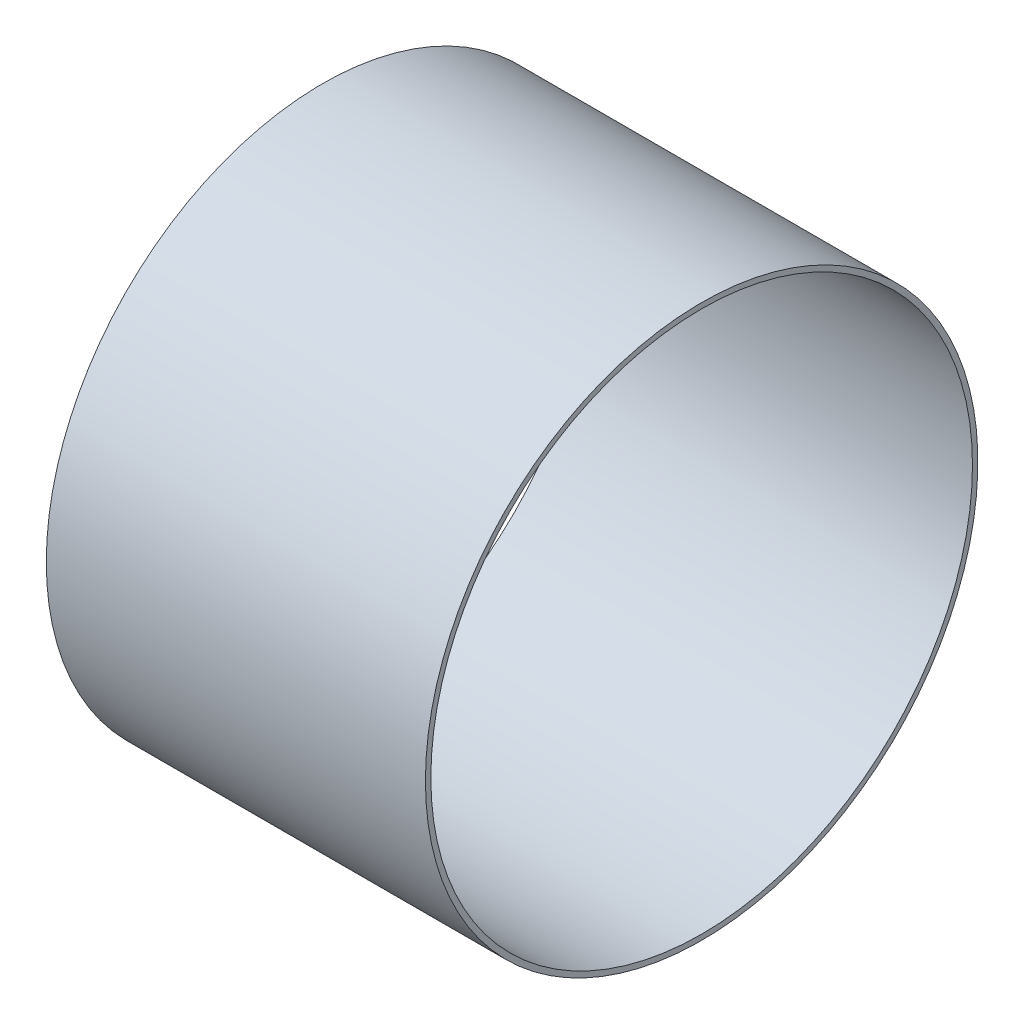
SolidWorks part; units mm, degrees
material "AISI 304"
ref_plane "Спереди" through (0, 0, 0) normal (0, 0, 1) x (1, 0, 0)
ref_plane "Сверху" through (0, 0, 0) normal (0, 1, 0) x (1, 0, 0)
ref_plane "Справа" through (0, 0, 0) normal (1, 0, 0) x (0, 0, -1)
ref_axis "Ось1" through (0, 0, 0) along (1, 0, 0)
sketch "Эскиз1" plane through (0, 0, 0) normal (0, 0, 1) x (1, 0, 0)
  line L0 (0, 0) -> (0, 101) construction
  line L1 (0, 101) -> (70, 101) construction
  line L2 (0, 0) -> (70, 0) construction
  line L3 (-70, 102) -> (70, 102)
  line L4 (-70, 102) -> (-70, 100)
  line L5 (-70, 100) -> (70, 100)
  line L6 (70, 102) -> (70, 100)
  point P9 (70.631, 0)
  dimension "D1" = 2
  dimension "D2" = 204
  dimension "D3" = 140
revolve "Повернуть1" add sketch "Эскиз1" angle 360 about L2
